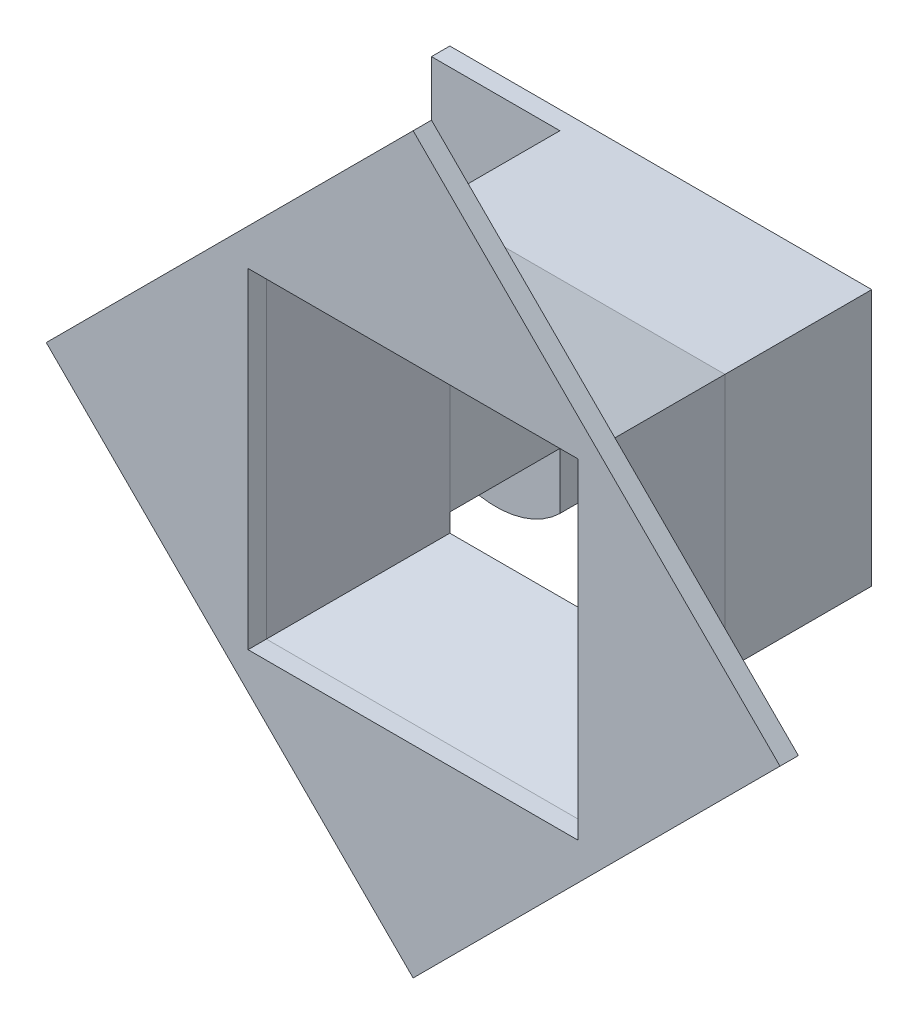
SolidWorks part; units mm, degrees
material "ABS"
ref_plane "Front Plane" through (0, 0, 0) normal (0, 0, 1) x (1, 0, 0)
ref_plane "Top Plane" through (0, 0, 0) normal (0, 1, 0) x (1, 0, 0)
ref_plane "Right Plane" through (0, 0, 0) normal (1, 0, 0) x (0, 0, -1)
sketch "Sketch2" plane through (0, 0, 0) normal (0, 0, 1) x (1, 0, 0)
  line L0 (0, 0) -> (69.8407, 0) construction
  line L1 (-50.8, 50.8) -> (50.8, 50.8)
  line L2 (-50.8, 50.8) -> (-50.8, -50.8)
  line L3 (-50.8, -50.8) -> (50.8, -50.8)
  line L4 (50.8, 50.8) -> (50.8, -50.8)
  line L5 (0, 0) -> (0, -80.5593) construction
  dimension "D1" = 101.6
ref_plane "Plane1" through (0, 0, 50.8) normal (0, 0, 1) x (1, 0, 0)
sketch "Sketch3" plane through (0, 0, 50.8) normal (0, 0, 1) x (1, 0, 0)
  line L0 (0, 0) -> (0, 42.9934) construction
  line L1 (-63.5, 63.5) -> (63.5, 63.5)
  line L2 (-63.5, 63.5) -> (-63.5, -63.5)
  line L3 (-63.5, -63.5) -> (63.5, -63.5)
  line L4 (63.5, 63.5) -> (63.5, -63.5)
  line L7 (0, 0) -> (38.1349, 0) construction
  dimension "D1" = 127
loft "Loft1" add profiles "Sketch2", "Sketch3" connector at (50.8, 50.8, 0) connector at (63.5, 63.5, 50.8)
sketch "Sketch4" plane through (0, 0, 50.8) normal (0, 0, 1) x (1, 0, 0)
  line L14 (-57.15, -57.15) -> (57.15, -57.15)
  line L15 (57.15, -57.15) -> (57.15, 57.15)
  line L16 (57.15, 57.15) -> (-57.15, 57.15)
  line L17 (-57.15, 57.15) -> (-57.15, -57.15)
  line L18 (-57.15, -57.15) -> (57.15, -57.15)
  line L19 (57.15, -57.15) -> (57.15, 57.15)
  line L20 (57.15, 57.15) -> (-57.15, 57.15)
  line L21 (-57.15, 57.15) -> (-57.15, -57.15)
  dimension "D1" = 6.35
sketch "Sketch5" plane through (0, 0, 0) normal (0, 0, -1) x (-1, 0, 0)
  line L14 (-44.45, -44.45) -> (44.45, -44.45)
  line L15 (44.45, -44.45) -> (44.45, 44.45)
  line L16 (44.45, 44.45) -> (-44.45, 44.45)
  line L17 (-44.45, 44.45) -> (-44.45, -44.45)
  line L18 (-44.45, -44.45) -> (44.45, -44.45)
  line L19 (44.45, -44.45) -> (44.45, 44.45)
  line L20 (44.45, 44.45) -> (-44.45, 44.45)
  line L21 (-44.45, 44.45) -> (-44.45, -44.45)
  dimension "D1" = 6.35
loft "Cut-Loft1" cut profiles "Sketch5", "Sketch4" connector at (-44.45, 44.45, 0) connector at (-57.15, 57.15, 50.8)
sketch "Sketch6" plane through (0, 0, 0) normal (0, 0, -1) x (-1, 0, 0)
  line L0 (44.45, -38.1) -> (50.8, -38.1)
  line L1 (44.45, -44.45) -> (44.45, 44.45) construction
  line L2 (50.8, 50.8) -> (50.8, -50.8) construction
  line L3 (50.8, -38.1) -> (50.8, 50.8)
  line L4 (50.8, 50.8) -> (-50.8, 50.8)
  line L5 (-50.8, 50.8) -> (-50.8, -38.1)
  line L6 (-50.8, -50.8) -> (-50.8, 50.8) construction
  line L7 (-50.8, -38.1) -> (-44.45, -38.1)
  line L8 (-44.45, 44.45) -> (-44.45, -44.45) construction
  line L9 (-44.45, -38.1) -> (-44.45, 44.45)
  line L10 (-44.45, 44.45) -> (44.45, 44.45)
  line L11 (44.45, 44.45) -> (44.45, -38.1)
  line L12 (44.45, -38.1) -> (38.1, -38.1) construction
  line L13 (-44.45, -38.1) -> (-38.1, -38.1) construction
extrude "Boss-Extrude1" add sketch "Sketch6" along normal blind 50.8
sketch "Sketch7" plane through (0, 0, -50.8) normal (0, 0, -1) x (-1, 0, 0)
  line L0 (50.8, 50.8) -> (-50.8, 50.8) construction
  line L1 (44.45, -38.1) -> (95.25, -38.1)
  line L2 (44.45, -38.1) -> (44.45, 50.8)
  line L3 (44.45, 50.8) -> (95.25, 50.8)
  line L4 (95.25, -38.1) -> (95.25, 50.8)
  dimension "D1" = 50.8
extrude "Boss-Extrude2" add sketch "Sketch7" against normal blind 6.35
sketch "Sketch8" plane through (0, 0, -44.45) normal (0, 0, 1) x (1, 0, 0)
  line L0 (-50.8, 50.8) -> (-50.8, -38.1) construction
  line L1 (-95.25, -38.1) -> (-50.8, -38.1)
  line L2 (-95.25, -38.1) -> (-95.25, -76.2)
  line L3 (-95.25, -76.2) -> (-50.8, -76.2)
  line L4 (-50.8, -38.1) -> (-50.8, -76.2)
  dimension "D1" = 38.1
extrude "Boss-Extrude3" add sketch "Sketch8" against normal up to surface (6.35 mm away) up to face at (-11.1125, 4.7625, -50.8)
fillet "Fillet1" [suppressed] radius 35.56
sketch "Sketch9" plane through (0, 0, -44.45) normal (0, 0, 1) x (1, 0, 0)
  line L0 (-73.025, 27.6092) -> (-73.025, -57.5144) construction
  line L3 (-62.992, -50.3) -> (-62.992, -11.041) construction
  line L4 (-83.185, -10.3505) -> (-62.865, -10.3505)
  line L5 (-83.185, -10.3505) -> (-83.185, -50.9905)
  line L6 (-83.185, -50.9905) -> (-62.865, -50.9905)
  line L7 (-62.865, -10.3505) -> (-62.865, -50.9905)
  line L8 (-83.058, -11.041) -> (-83.058, -50.3) construction
  line L9 (-89.9768, -30.6705) -> (-55.7405, -30.6705) construction
  line L10 (-82.558, -50.8) -> (-63.492, -50.8) construction
  line L11 (-63.492, -10.541) -> (-82.558, -10.541) construction
  dimension "D1" = 20.32
  dimension "D2" = 40.64
fillet "Fillet2" [suppressed] radius 2.54
extrude "Cut-Extrude1" cut sketch "Sketch9" against normal through all
sketch "Sketch10" plane through (0, 0, -44.45) normal (0, 0, 1) x (1, 0, 0)
  circle A0 centre (-68.025, -6.1705) radius 1.778
  circle A1 centre (-78.025, -6.1705) radius 1.778
  circle A2 centre (-78.025, -55.1705) radius 1.778
  circle A3 centre (-68.025, -55.1705) radius 1.778
  arc A4 (-76.755, -56.4148) -> (-79.295, -56.4148) centre (-78.025, -55.1705) ccw construction
  arc A5 (-66.755, -56.4148) -> (-69.295, -56.4148) centre (-68.025, -55.1705) ccw construction
  arc A6 (-79.295, -4.9262) -> (-76.755, -4.9262) centre (-78.025, -6.1705) ccw construction
  arc A7 (-69.295, -4.9262) -> (-66.755, -4.9262) centre (-68.025, -6.1705) ccw construction
extrude "Cut-Extrude2" cut sketch "Sketch10" against normal through all
sketch "Sketch11" plane through (0, 0, -44.45) normal (0, 0, 1) x (1, 0, 0)
  line L0 (-50.8, -76.2) -> (-95.25, -76.2)
  line L1 (-95.25, -76.2) -> (-50.8, -76.2) construction
  line L2 (-95.25, -76.2) -> (-95.25, -63.949)
  line L3 (-95.25, -76.2) -> (-95.25, 50.8) construction
  line L4 (-50.8, -76.2) -> (-50.8, -63.949)
  line L5 (-50.8, -76.2) -> (-50.8, -38.1) construction
  circle A0 centre (-73.025, -41.275) radius 31.75
  circle A1 centre (-73.025, -41.275) radius 6.25 construction
  line M11 (-95.25, 50.8) -> (-95.25, -76.2)
  line M12 (-95.25, -76.2) -> (-50.8, -76.2)
  line M13 (-50.8, -76.2) -> (-50.8, -38.1)
  dimension "D1" = 63.5
extrude "Cut-Extrude3" cut sketch "Sketch11" against normal blind 6.35 contours A0 M11 M12 M13 region at (-73.025, -75.7389, -44.45)
sketch "Sketch12" plane through (0, 0, 50.8) normal (0, 0, 1) x (1, 0, 0)
  line L0 (127, 0) -> (0, -127)
  line L1 (127, 0) -> (0, 127)
  line L2 (0, -127) -> (-127, 0)
  line L3 (0, 127) -> (-127, 0)
  line L4 (-63.5, -63.5) -> (63.5, -63.5) construction
  line L5 (0, 0) -> (-106.6892, -106.6892) construction
  line L6 (0, 0) -> (125.9109, -125.9109) construction
  line L7 (63.5, -63.5) -> (63.5, 63.5) construction
  line L8 (-63.5, 63.5) -> (-63.5, -63.5) construction
  line L9 (63.5, 63.5) -> (-63.5, 63.5) construction
  line L10 (63.5, -63.5) -> (63.5, 63.5)
  line L11 (-63.5, -63.5) -> (63.5, -63.5)
  line L12 (-63.5, 63.5) -> (-63.5, -63.5)
  line L13 (63.5, 63.5) -> (-63.5, 63.5)
  line L14 (57.15, -57.15) -> (57.15, 57.15) construction
  line L15 (-57.15, -57.15) -> (57.15, -57.15) construction
  line L16 (-57.15, 57.15) -> (-57.15, -57.15) construction
  line L17 (57.15, 57.15) -> (-57.15, 57.15) construction
  line L18 (57.15, -57.15) -> (57.15, 57.15)
  line L19 (-57.15, -57.15) -> (57.15, -57.15)
  line L20 (-57.15, 57.15) -> (-57.15, -57.15)
  line L21 (57.15, 57.15) -> (-57.15, 57.15)
  line M11 (57.15, -57.15) -> (-57.15, -57.15)
  line M12 (-57.15, -57.15) -> (-57.15, 57.15)
  line M13 (-57.15, 57.15) -> (57.15, 57.15)
  line M14 (57.15, 57.15) -> (57.15, -57.15)
  dimension "D1" = 45
extrude "Boss-Extrude5" add sketch "Sketch12" along normal blind 6.35 contours L0 L1 | M14 M11 M12 M13 | L2 L0 | L3 L2 | L1 L3 region at (84.6667, 0, 50.8) region at (0, -61.7039, 50.8) region at (0, -84.6667, 50.8) region at (0, 84.6667, 50.8) region at (-84.6667, 0, 50.8)
